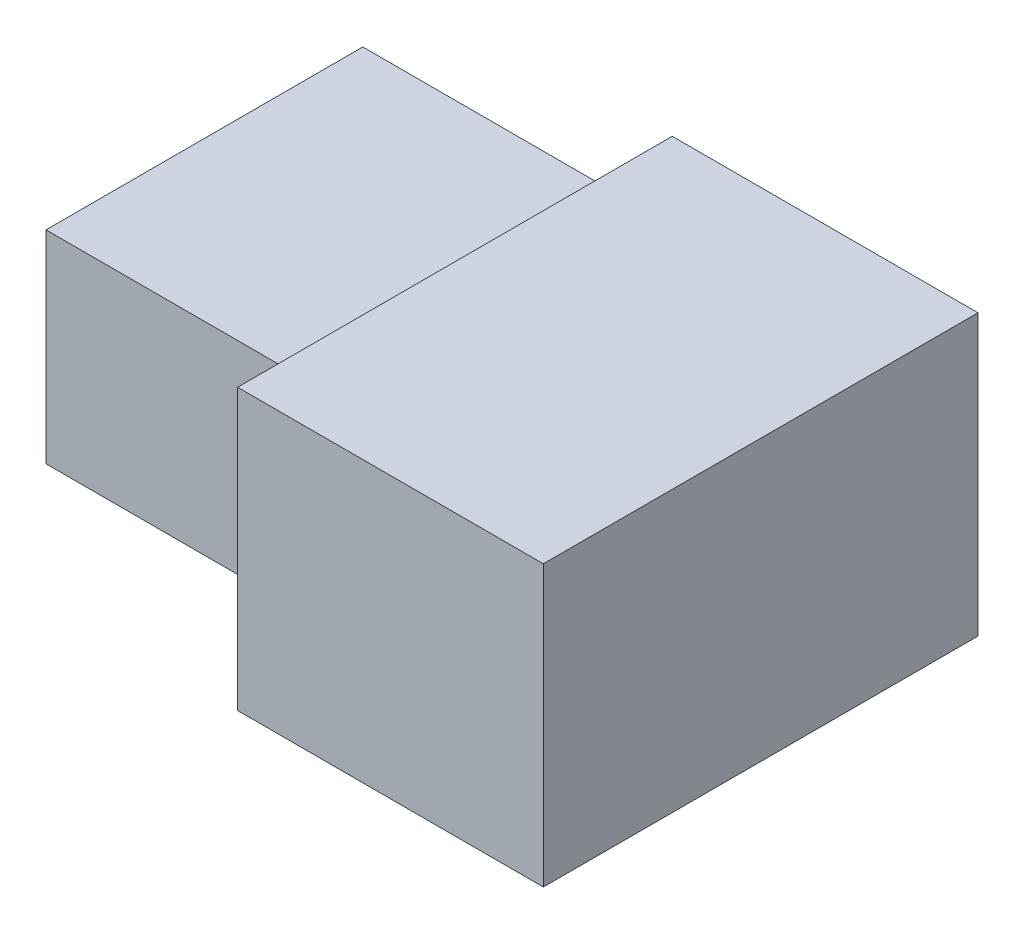
SolidWorks part; units mm, degrees
ref_plane "Front" through (0, 0, 0) normal (0, 0, 1) x (1, 0, 0)
ref_plane "Top" through (0, 0, 0) normal (0, 1, 0) x (1, 0, 0)
ref_plane "Right" through (0, 0, 0) normal (1, 0, 0) x (0, 0, -1)
sketch "Sketch1" plane through (0, 0, 0) normal (0, 1, 0) x (1, 0, 0)
  line L1 (0, 0) -> (83, 0)
  line L2 (0, 0) -> (0, -118)
  line L3 (0, -118) -> (83, -118)
  line L4 (83, 0) -> (83, -118)
  line L5 (0, 0) -> (-84, 0)
  line L6 (0, 0) -> (0, -86)
  line L7 (0, -86) -> (-84, -86)
  line L8 (-84, 0) -> (-84, -86)
  point P8 (-126.1966, -97.4183)
  dimension "D1" = 83
  dimension "D2" = 118
  dimension "D3" = 86
  dimension "D4" = 84
extrude "Boss-Extrude1" add sketch "Sketch1" along normal blind 76 contours L4 L1 L2 L3 region at (41.5, 0, 59)
extrude "Boss-Extrude2" add sketch "Sketch1<3>" along normal blind 55 contours L5 L8 L7 L2 region at (-42, 0, 43)
sketch "Sketch1<3>" plane through (0, 0, 0) normal (0, 1, 0) x (1, 0, 0) same geometry as "Sketch1"
